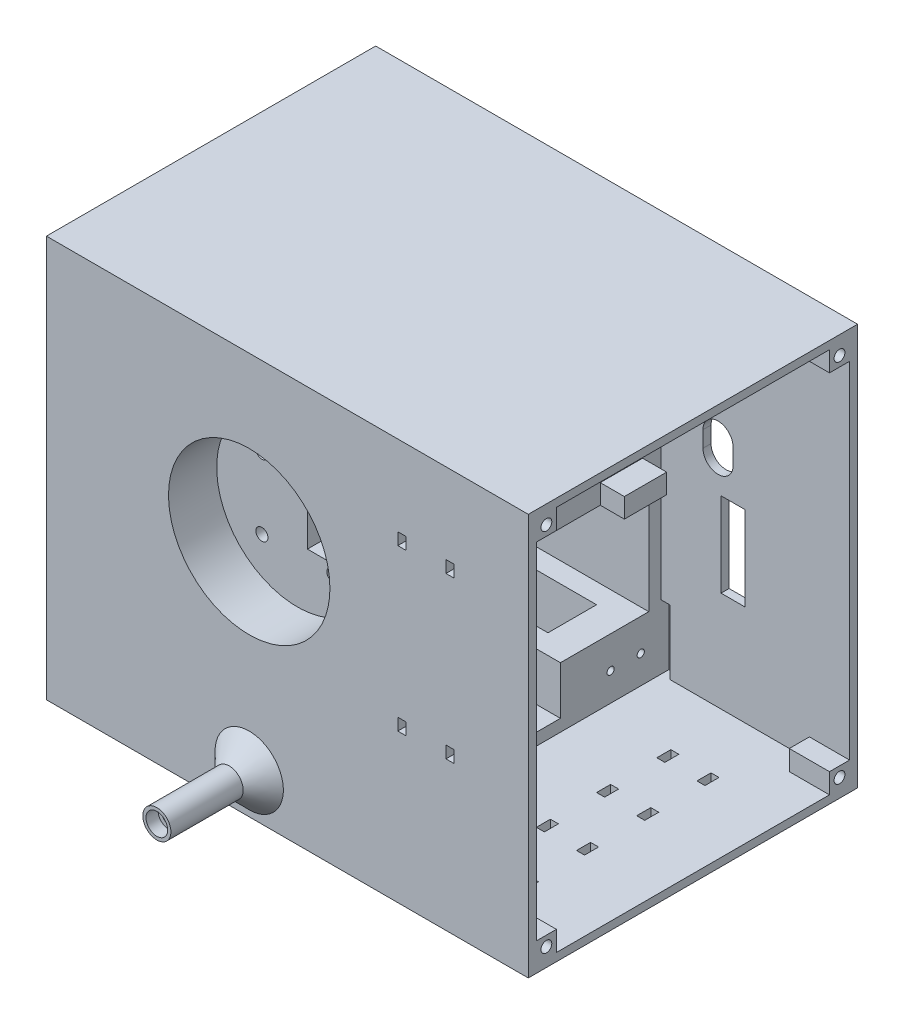
SolidWorks part; units mm, degrees
ref_plane "Plan de face" through (0, 0, 0) normal (0, 0, 1) x (1, 0, 0)
ref_plane "Plan de dessus" through (0, 0, 0) normal (0, 1, 0) x (1, 0, 0)
ref_plane "Plan de droite" through (0, 0, 0) normal (1, 0, 0) x (0, 0, -1)
sketch "Esquisse1" plane through (0, 0, 0) normal (0, 0, 1) x (1, 0, 0)
  line L0 (8.8388, 18.2) -> (8.8388, 0.5223) construction
  line L5 (-22.5, 50) -> (22.5, -50) construction
  line L6 (-22.5, -50) -> (22.5, 50) construction
  line L7 (-10.15, 45) -> (10.15, 45) construction
  line L8 (-10.15, 45) -> (-10.15, 24.7) construction
  line L9 (-10.15, 24.7) -> (10.15, 24.7) construction
  line L10 (10.15, 45) -> (10.15, 24.7) construction
  line L11 (-10.15, 45) -> (10.15, 24.7) construction
  line L12 (-10.15, 24.7) -> (10.15, 45) construction
  line L13 (8.8388, 0.5223) -> (-8.8388, 0.5223) construction
  line L15 (-22.5, 50) -> (22.5, 50)
  line L16 (-22.5, 50) -> (-22.5, -50)
  line L17 (-22.5, -50) -> (22.5, -50)
  line L18 (22.5, 50) -> (22.5, -50)
  circle A0 centre (0, 9.3612) radius 20.1
  circle A1 centre (0, 9.3612) radius 12.5 construction
  circle A2 centre (8.8388, 18.2) radius 1.5
  circle A3 centre (8.8388, 0.5223) radius 1.5
  circle A4 centre (-8.8388, 0.5223) radius 1.5
  circle A5 centre (-8.8388, 18.2) radius 1.5
  circle A6 centre (8.8388, 18.2) radius 3.5 construction
  point P7 (0, 34.85)
  point P32 (0, 0)
  dimension "D1" = 40.2
  dimension "D6" = 3
  dimension "D7" = 25
  dimension "D8" = 7
  dimension "D5" = 6.5
  dimension "D2" = 100
  dimension "D3" = 45
  dimension "D4" = 20.3
  dimension "D9" = 5
extrude "Boss.-Extru.1" add sketch "Esquisse1" along normal blind 12 contours L18 L15 L16 L17 A0 L7 L10 L9 L8 | L10 L7 L8 L9 region at (0, 48.9034, 0)
extrude "Boss.-Extru.4" add sketch "Esquisse1<3>" against normal blind 5 contours A0 | L18 L15 L16 L17 A0 L7 L10 L9 L8 region at (0, 48.9034, 0) region at (0, 9.3612, 0)
sketch "Esquisse1<3>" plane through (0, 0, 0) normal (0, 0, 1) x (1, 0, 0) same geometry as "Esquisse1"
sketch "Esquisse4" plane through (0, 0, -5) normal (0, 0, -1) x (-1, 0, 0)
  line L2 (-10, 45) -> (10, 25) construction
  line L4 (-22.5, 50) -> (-22.5, -50)
  line L5 (-22.5, -50) -> (22.5, -50)
  line L6 (22.5, -50) -> (22.5, 50)
  line L7 (22.5, 50) -> (-22.5, 50)
  line L8 (-22.5, 50) -> (-22.5, -50)
  line L9 (-22.5, -50) -> (22.5, -50)
  line L10 (22.5, -50) -> (22.5, 50)
  line L11 (22.5, 50) -> (-22.5, 50)
  line L15 (-10, 45) -> (10, 45)
  line L19 (-10, 45) -> (-10, 25)
  line L20 (-10, 25) -> (10, 25)
  line L21 (10, 45) -> (10, 25)
  circle A1 centre (8.8388, 18.2) radius 3.5
  circle A2 centre (8.8388, 0.5223) radius 3.5
  circle A3 centre (-8.8388, 0.5223) radius 3.5
  circle A4 centre (-8.8388, 18.2) radius 3.5
  point P17 (0, 35)
  line M10 (-22.5, 50) -> (-22.5, -50)
  line M11 (-22.5, -50) -> (22.5, -50)
  line M12 (22.5, -50) -> (22.5, 50)
  line M13 (22.5, 50) -> (-22.5, 50)
  dimension "D2" = 7
  dimension "D3" = 20
  dimension "D4" = 5
  dimension "D1" = 0
extrude "Boss.-Extru.5" add sketch "Esquisse4" along normal blind 65 contours A1 M13 M10 M11 M12 region at (0, -3.913, -5)
ref_plane "Plan1" through (-14.5, -50, -60) normal (0, 0, 1) x (1, 0, 0)
sketch "Esquisse6" plane through (0, -50, 0) normal (0, -1, 0) x (1, 0, 0)
  line L0 (0, -70) -> (0, 12) construction
  line L1 (22.5, -70) -> (-22.5, -70) construction
  line L2 (-22.5, 12) -> (22.5, 12) construction
  line L3 (-14.5, -47.9) -> (14.5, -47.9)
  line L4 (-14.5, -47.9) -> (-14.5, -60)
  line L5 (-14.5, -60) -> (14.5, -60)
  line L6 (14.5, -47.9) -> (14.5, -60)
  line L7 (-14.5, -47.9) -> (14.5, -60) construction
  line L8 (-14.5, -60) -> (14.5, -47.9) construction
  point P5 (0, -53.95)
  dimension "D1" = 12.1
  dimension "D2" = 29
  dimension "D3" = 10
extrude "Enlèv. mat.-Extru.1" cut sketch "Esquisse6" against normal blind 46
sketch "Esquisse7" plane through (-22.5, 0, 0) normal (-1, 0, 0) x (0, 0, 1)
  line L0 (12, 50) -> (-70, -50) construction
  line L1 (12, 50) -> (-70, 50)
  line L2 (12, 50) -> (12, -50)
  line L3 (12, -50) -> (-70, -50)
  line L4 (-70, 50) -> (-70, -50)
  line L5 (10, 48) -> (10, -48)
  line L10 (8.1701, 41.2587) -> (-66.1701, -41.2587) construction
  line L11 (8.1701, -41.2587) -> (-66.1701, 41.2587) construction
  line L12 (10, -48) -> (-68, -48)
  line L13 (-68, 48) -> (-68, -48)
  line L14 (10, 48) -> (-68, 48)
  point P6 (-29, 0)
  dimension "D1" = 2
extrude "Boss.-Extru.6" add sketch "Esquisse7" along normal blind 28
sketch "Esquisse8" plane through (22.5, 0, 0) normal (1, 0, 0) x (0, 0, -1)
  line L0 (-12, -50) -> (70, 50) construction
  line L1 (-10, -48) -> (-10, 48)
  line L2 (-12, -50) -> (70, -50)
  line L3 (-12, -50) -> (-12, 50)
  line L4 (-12, 50) -> (70, 50)
  line L5 (70, -50) -> (70, 50)
  line L6 (-10, 48) -> (68, 48)
  line L7 (68, -48) -> (68, 48)
  line L8 (-10, -48) -> (68, -48)
  dimension "D1" = 2
extrude "Boss.-Extru.7" add sketch "Esquisse8" along normal blind 47
sketch "Esquisse9" plane through (22.5, 0, 0) normal (1, 0, 0) x (0, 0, -1)
  line L0 (-10, 48) -> (-10, -48) construction
  line L1 (-4, 3) -> (6, 3)
  line L2 (-4, 3) -> (-4, 15.5)
  line L3 (-4, 15.5) -> (6, 15.5)
  line L4 (6, 3) -> (6, 15.5)
  line L5 (68, 48) -> (-10, 48) construction
  dimension "D1" = 12.5
  dimension "D2" = 10
  dimension "D3" = 6
  dimension "D4" = 32.5
extrude "Enlèv. mat.-Extru.2" cut sketch "Esquisse9" against normal blind 20
sketch "Esquisse10" plane through (0, 0, 10) normal (0, 0, -1) x (-1, 0, 0)
  line L0 (-44, 48) -> (-44, -48) construction
  line L1 (-69.5, 48) -> (-22.5, 48) construction
  line L2 (-69.5, -48) -> (-22.5, -48) construction
  line L3 (-22.5, -48) -> (-22.5, 48) construction
  line L4 (-69.5, -48) -> (-22.5, -48) construction
  line L5 (-49, -13) -> (-51, -13)
  line L6 (-49, -13) -> (-49, -10)
  line L7 (-49, -10) -> (-51, -10)
  line L8 (-51, -13) -> (-51, -10)
  line L9 (-49, 27) -> (-49, 30)
  line L10 (-49, 27) -> (-51, 27)
  line L11 (-51, 27) -> (-51, 30)
  line L12 (-49, 30) -> (-51, 30)
  line L13 (-49, -13) -> (-49, 27) construction
  line L14 (-37, -13) -> (-37, -10)
  line L15 (-39, -10) -> (-37, -10)
  line L16 (-39, -13) -> (-39, -10)
  line L17 (-39, -13) -> (-37, -13)
  line L18 (-39, -13) -> (-39, 27) construction
  line L19 (-39, 30) -> (-37, 30)
  line L20 (-37, 27) -> (-37, 30)
  line L21 (-39, 27) -> (-37, 27)
  line L22 (-39, 27) -> (-39, 30)
  dimension "D1" = 21.5
  dimension "D2" = 5
  dimension "D3" = 3
  dimension "D4" = 2
  dimension "D5" = 35
  dimension "D7" = 40
  dimension "D6" = 2
extrude "Enlèv. mat.-Extru.3" cut sketch "Esquisse10" against normal up to next
sketch "Esquisse11" plane through (22.5, 0, 0) normal (1, 0, 0) x (0, 0, -1)
  line L0 (-7, -45) -> (43, -45)
  line L5 (43, -45) -> (43, -33)
  line L6 (43, -33) -> (65, -33)
  line L7 (65, -33) -> (65, -4)
  line L8 (65, -4) -> (18, -4)
  line L9 (18, -4) -> (18, -20)
  line L10 (18, -20) -> (-7, -20)
  line L11 (-7, -20) -> (-7, -45)
  line L12 (-10, -48) -> (68, -48) construction
  line L13 (-10, 48) -> (-10, -48) construction
  line L14 (68, -48) -> (68, 48) construction
  dimension "D1" = 3
  dimension "D2" = 3
  dimension "D3" = 25
  dimension "D4" = 3
  dimension "D5" = 15
  dimension "D6" = 25
  dimension "D7" = 25
  dimension "D8" = 41
extrude "Enlèv. mat.-Extru.4" cut sketch "Esquisse11" against normal blind 40
sketch "Esquisse12" plane through (-17.5, 0, 0) normal (1, 0, 0) x (0, 0, -1)
  line L0 (62, -32) -> (-4, -32) construction
  line L1 (-7, -45) -> (43, -45)
  line L2 (-7, -45) -> (-7, -32)
  line L3 (-7, -32) -> (43, -32)
  line L4 (43, -45) -> (43, -32)
  line L5 (43, -45) -> (43, -33) construction
extrude "Enlèv. mat.-Extru.5" cut sketch "Esquisse12" against normal up to next
sketch "Esquisse13" plane through (0, -50, 0) normal (0, -1, 0) x (1, 0, 0)
  line L0 (46, -68) -> (46, 10) construction
  line L1 (69.5, -68) -> (22.5, -68) construction
  line L2 (69.5, 10) -> (22.5, 10) construction
  line L3 (50, -38) -> (50, -34.5)
  line L4 (50, -53) -> (52, -53)
  line L5 (50, -53) -> (50, -49.5)
  line L6 (50, -49.5) -> (52, -49.5)
  line L7 (52, -53) -> (52, -49.5)
  line L8 (50, -38) -> (52, -38)
  line L9 (52, -38) -> (52, -34.5)
  line L10 (50, -34.5) -> (52, -34.5)
  line L11 (50, -23) -> (50, -19.5)
  line L12 (50, -23) -> (52, -23)
  line L13 (52, -23) -> (52, -19.5)
  line L14 (50, -19.5) -> (52, -19.5)
  line L15 (50, -8) -> (50, -4.5)
  line L16 (50, -8) -> (52, -8)
  line L17 (52, -8) -> (52, -4.5)
  line L18 (50, -4.5) -> (52, -4.5)
  line L19 (50, -53) -> (50, -38) construction
  line L20 (42, -53) -> (42, -38) construction
  line L21 (42, -4.5) -> (40, -4.5)
  line L22 (40, -8) -> (40, -4.5)
  line L23 (42, -8) -> (40, -8)
  line L24 (42, -8) -> (42, -4.5)
  line L25 (42, -19.5) -> (40, -19.5)
  line L26 (40, -23) -> (40, -19.5)
  line L27 (42, -23) -> (40, -23)
  line L28 (42, -23) -> (42, -19.5)
  line L29 (42, -34.5) -> (40, -34.5)
  line L30 (40, -38) -> (40, -34.5)
  line L31 (42, -38) -> (40, -38)
  line L32 (40, -53) -> (40, -49.5)
  line L33 (42, -49.5) -> (40, -49.5)
  line L34 (42, -53) -> (42, -49.5)
  line L35 (42, -53) -> (40, -53)
  line L36 (42, -38) -> (42, -34.5)
  dimension "D1" = 4
  dimension "D2" = 2
  dimension "D3" = 3.5
  dimension "D4" = 15
  dimension "D6" = 15
  dimension "D5" = 4
extrude "Enlèv. mat.-Extru.6" cut sketch "Esquisse13" against normal up to next
sketch "Esquisse14" plane through (22.5, 0, 0) normal (1, 0, 0) x (0, 0, -1)
  line L5 (-10, -48) -> (68, -48) construction
  line L6 (68, -48) -> (68, 48) construction
  circle A0 centre (14, -12) radius 3.5
  circle A1 centre (14, -12) radius 1.375
  circle A3 centre (60, 38) radius 3.5
  circle A4 centre (60, 38) radius 1.375
  dimension "D1" = 2.75
  dimension "D2" = 7
  dimension "D3" = 36
  dimension "D4" = 54
  dimension "D5" = 46
  dimension "D6" = 50
extrude "Boss.-Extru.8" add sketch "Esquisse14" along normal blind 6
sketch "Esquisse15" plane through (22.5, 0, 0) normal (1, 0, 0) x (0, 0, -1)
  line L0 (65, -4) -> (18, -4) construction
  line L1 (63.4544, -4) -> (52.9202, -4)
  line L2 (63.4544, -4) -> (63.4544, 0.874)
  line L3 (63.4544, 0.874) -> (52.9202, 0.874)
  line L4 (52.9202, -4) -> (52.9202, 0.874)
  line L6 (11, 41) -> (19.6788, 41)
  line L7 (11, 41) -> (11, 30.8965)
  line L8 (11, 30.8965) -> (19.6788, 30.8965)
  line L9 (19.6788, 41) -> (19.6788, 30.8965)
extrude "Boss.-Extru.9" add sketch "Esquisse15" along normal blind 6
sketch "Esquisse17" plane through (0, 0, -68) normal (0, 0, 1) x (1, 0, 0)
  line L1 (37.5, -23) -> (43.5, -23)
  line L2 (37.5, -23) -> (37.5, -2)
  line L3 (37.5, -2) -> (43.5, -2)
  line L4 (43.5, -23) -> (43.5, -2)
  line L5 (22.5, -48) -> (22.5, 48) construction
  line L6 (69.5, -48) -> (22.5, -48) construction
  dimension "D1" = 6
  dimension "D2" = 21
  dimension "D3" = 15
  dimension "D4" = 25
extrude "Enlèv. mat.-Extru.7" cut sketch "Esquisse17" against normal up to next
sketch "Esquisse19" plane through (0, 0, 12) normal (0, 0, 1) x (1, 0, 0)
  line L1 (-50.5, -50) -> (69.5, -50) construction
  circle A0 centre (0, -40) radius 3.5
  circle A1 centre (0, -40) radius 1.7
  dimension "D1" = 7
  dimension "D3" = 3.4
  dimension "D2" = 10
extrude "Boss.-Extru.10" add sketch "Esquisse19" along normal blind 23
extrude "Enlèv. mat.-Extru.8" cut sketch "Esquisse19<2>" against normal up to next contours A1 region at (0, -40, 12)
sketch "Esquisse19<2>" plane through (0, 0, 12) normal (0, 0, 1) x (1, 0, 0) same geometry as "Esquisse19"
sketch "Esquisse20" plane through (0, 0, 35) normal (0, 0, 1) x (1, 0, 0)
  circle A0 centre (0, -40) radius 2.7
  dimension "D1" = 5.4
extrude "Enlèv. mat.-Extru.9" cut sketch "Esquisse20" against normal blind 3
sketch "Esquisse21" plane through (0, 0, 7) normal (0, 0, -1) x (-1, 0, 0)
  line L1 (-1.6166, -42.8) -> (1.6166, -42.8)
  line L2 (1.6166, -42.8) -> (3.2332, -40)
  line L3 (3.2332, -40) -> (1.6166, -37.2)
  line L4 (1.6166, -37.2) -> (-1.6166, -37.2)
  line L5 (-1.6166, -37.2) -> (-3.2332, -40)
  line L6 (-3.2332, -40) -> (-1.6166, -42.8)
  circle A0 centre (0, -40) radius 2.8 construction
  dimension "D1" = 5.6
extrude "Enlèv. mat.-Extru.10" cut sketch "Esquisse21" against normal blind 2.5
chamfer "Chanfrein1" distance 5 angle 45 1 edges at (3.5, -40, 12)
sketch "Esquisse23" plane through (0, 0, -70) normal (0, 0, -1) x (-1, 0, 0)
  line L0 (50.5, 50) -> (-69.5, 50) construction
  line L1 (-40.5, 13.75) -> (-33, 13.75)
  line L2 (-40.5, 13.75) -> (-40.5, 2.25)
  line L3 (-40.5, 2.25) -> (-33, 2.25)
  line L4 (-33, 13.75) -> (-33, 2.25)
  line L5 (-69.5, -50) -> (-69.5, 50) construction
  line L6 (-40.5, 8) -> (-33, 8) construction
  arc A0 (-40.5, 10) -> (-33, 10) centre (-36.75, 10) cw
  arc A1 (-40.5, 6) -> (-33, 6) centre (-36.75, 6) ccw
  dimension "D1" = 11.5
  dimension "D2" = 7.5
  dimension "D3" = 36.25
  dimension "D4" = 29
extrude "Enlèv. mat.-Extru.11" cut sketch "Esquisse23" against normal up to surface (2 mm away) contours L2 L6 L4 A0 | L6 L2 A1 L4 region at (36.75, 10.5435, -70) region at (36.75, 5.4565, -70) up to face at (40.5, -12.5, -68)
sketch "Esquisse24" plane through (-22.5, 0, 0) normal (-1, 0, 0) x (0, 0, 1)
  line L0 (7, -32) -> (-43, -32) construction
  line L1 (10, 48) -> (4.5, 48)
  line L2 (10, 48) -> (10, -32)
  line L3 (10, -32) -> (4.5, -32)
  line L4 (4.5, 48) -> (4.5, -32)
  line L6 (-68, 48) -> (-62.5, 48)
  line L7 (-68, 48) -> (-68, -32)
  line L8 (-68, -32) -> (-62.5, -32)
  line L9 (-62.5, 48) -> (-62.5, -32)
  dimension "D1" = 5.5
  dimension "D2" = 5.5
extrude "Boss.-Extru.11" add sketch "Esquisse24" along normal up to surface (28 mm away) up to face at (-50.5, 0, -29)
sketch "Esquisse25" plane through (0, 0, -68) normal (0, 0, 1) x (1, 0, 0)
  line L1 (-50.5, -48) -> (-45.5, -48)
  line L2 (-50.5, -48) -> (-50.5, -41)
  line L3 (-50.5, -41) -> (-45.5, -41)
  line L4 (-45.5, -48) -> (-45.5, -41)
  dimension "D1" = 7
  dimension "D2" = 5
extrude "Enlèv. mat.-Extru.12" cut sketch "Esquisse25" against normal up to surface (2 mm away) up to face at (36.75, 8, -70)
sketch "Esquisse26" plane through (0, 0, -70) normal (0, 0, -1) x (-1, 0, 0)
  line L1 (-22.5, -48) -> (-24.8, -48)
  line L2 (-22.5, -48) -> (-22.5, -31.9)
  line L3 (-22.5, -31.9) -> (-24.8, -31.9)
  line L4 (-24.8, -48) -> (-24.8, -31.9)
  dimension "D1" = 2.3
  dimension "D2" = 16.1
extrude "Enlèv. mat.-Extru.13" cut sketch "Esquisse26" against normal up to surface (2 mm away) up to face at (36.75, 8, -68)
sketch "Esquisse27" plane through (22.5, 0, 0) normal (1, 0, 0) x (0, 0, -1)
  line L0 (68, -41) -> (50.9775, -41) construction
  line L1 (68, -48) -> (68, 48) construction
  line L2 (-10, -48) -> (68, -48) construction
  circle A0 centre (63, -41) radius 0.9
  circle A1 centre (55.5, -41) radius 0.9
  dimension "D3" = 1.8
  dimension "D1" = 7
  dimension "D2" = 5
  dimension "D4" = 7.5
extrude "Enlèv. mat.-Extru.14" cut sketch "Esquisse27" against normal blind 8
sketch "Esquisse28" plane through (69.5, 0, 0) normal (1, 0, 0) x (0, 0, -1)
  line L0 (-10, -48) -> (-5, -43) construction
  line L1 (-10, -48) -> (-5, -48)
  line L2 (-10, -48) -> (-10, -43)
  line L3 (-10, -43) -> (-5, -43)
  line L4 (-5, -48) -> (-5, -43)
  line L5 (-10, 0) -> (70, 0) construction
  line L6 (-10, 48) -> (-10, -48) construction
  line L7 (70, -50) -> (70, 50) construction
  line L8 (29, -48) -> (29, 48) construction
  line L9 (-10, -48) -> (68, -48) construction
  line L10 (68, 48) -> (-10, 48) construction
  line L11 (-10, 43) -> (-5, 43)
  line L12 (-5, 48) -> (-5, 43)
  line L13 (-10, 48) -> (-5, 48)
  line L14 (-10, 48) -> (-10, 43)
  line L15 (86, -48) -> (81, -48)
  line L16 (86, -48) -> (86, -43)
  line L17 (86, -43) -> (81, -43)
  line L18 (81, -48) -> (81, -43)
  line L19 (-10, -43) -> (-5, -43)
  line L20 (-5, -48) -> (-5, -43)
  line L21 (-10, -48) -> (-5, -48)
  line L22 (-10, -48) -> (-10, -43)
  line L23 (68, -48) -> (63, -43) construction
  line L24 (68, -48) -> (68, -43)
  line L25 (68, -48) -> (63, -48)
  line L26 (63, -48) -> (63, -43)
  line L27 (68, -43) -> (63, -43)
  line L28 (68, 48) -> (68, 43)
  line L29 (68, 48) -> (63, 48)
  line L30 (63, 48) -> (63, 43)
  line L31 (68, 43) -> (63, 43)
  line L32 (63, -48) -> (63, -43)
  line L33 (68, -43) -> (63, -43)
  line L34 (68, -48) -> (68, -43)
  line L35 (68, -48) -> (63, -48)
  circle A0 centre (-7.5, -45.5) radius 1.35
  circle A1 centre (-7.5, 45.5) radius 1.35
  circle A2 centre (83.5, -45.5) radius 1.35
  circle A3 centre (65.5, 45.5) radius 1.35
  circle A4 centre (65.5, -45.5) radius 1.35
  line M12 (68, -48) -> (-10, -48)
  line M13 (-10, -48) -> (-10, 48)
  line M14 (-10, 48) -> (68, 48)
  line M15 (68, 48) -> (68, -48)
  dimension "D1" = 2.7
  dimension "D2" = 5
extrude "Boss.-Extru.12" add sketch "Esquisse28" against normal blind 10 contours L4 L3 A0 M12 M13 | L12 L11 A1 M14 M13 | L31 L30 A3 M15 M14 | L27 L26 A4 M15 M12 region at (69.5, -45.5, 9.9293) region at (69.5, -45.5, -63.0707) region at (69.5, 45.5, 9.9293) region at (69.5, 43.0707, -65.5)
sketch "Esquisse29" plane through (-50.5, 0, 0) normal (-1, 0, 0) x (0, 0, 1)
  line L0 (-65.5, 45.5) -> (-65.5, -29.5) construction
  circle A0 centre (7.5, 45.5) radius 1.35
  circle A1 centre (-65.5, 45.5) radius 1.35
  circle A2 centre (7.5, 45.5) radius 1.35 construction
  circle A3 centre (-65.5, -29.5) radius 1.35
  circle A4 centre (7.5, -29.5) radius 1.35
  dimension "D2" = 75
  dimension "D1" = 2
extrude "Enlèv. mat.-Extru.15" cut sketch "Esquisse29" against normal blind 10
sketch "Esquisse30" plane through (0, 0, -70) normal (0, 0, -1) x (-1, 0, 0)
  line L0 (10, 45) -> (-10, 25) construction
  line L1 (-59.5, 48) -> (-22.5, 48) construction
  line L2 (-27.5, 24.7) -> (27.5, 24.7) construction
  line L3 (-27.5, 24.7) -> (-27.5, 45.3) construction
  line L4 (-27.5, 45.3) -> (27.5, 45.3) construction
  line L5 (27.5, 24.7) -> (27.5, 45.3) construction
  line L6 (-27.5, 24.7) -> (27.5, 45.3) construction
  line L7 (-27.5, 45.3) -> (27.5, 24.7) construction
  line L8 (-30.6177, 45.3) -> (-29.0588, 42.6) construction
  line L9 (-29.0588, 42.6) -> (-25.9412, 42.6) construction
  line L10 (-25.9412, 42.6) -> (-24.3823, 45.3) construction
  line L11 (-24.3823, 45.3) -> (-25.9412, 48) construction
  line L12 (-25.9412, 48) -> (-29.0588, 48) construction
  line L13 (-29.0588, 48) -> (-30.6177, 45.3) construction
  circle A0 centre (27.5, 45.3) radius 1.7
  circle A1 centre (27.5, 24.7) radius 1.7
  circle A2 centre (-27.5, 24.7) radius 1.7
  circle A3 centre (-27.5, 45.3) radius 1.7
  circle A4 centre (-27.5, 45.3) radius 2.7 construction
  point P4 (0, 35)
  dimension "D1" = 3.4
  dimension "D2" = 5.4
  dimension "D3" = 55
extrude "Enlèv. mat.-Extru.16" cut sketch "Esquisse30" against normal up to next
sketch "Esquisse31" plane through (0, 0, -68) normal (0, 0, 1) x (1, 0, 0)
  line L0 (32.5, 48) -> (22.5, 41) construction
  line L1 (22.5, 48) -> (32.5, 48)
  line L2 (22.5, 48) -> (22.5, 41)
  line L3 (22.5, 41) -> (32.5, 41)
  line L4 (32.5, 48) -> (32.5, 41)
  line L5 (27.5, 45.3) -> (27.5, 24.7) construction
  line L6 (27.5, 35) -> (22.5, 35) construction
  line L7 (22.5, 48) -> (22.5, -48) construction
  line L8 (59.5, 48) -> (22.5, 48) construction
  line L9 (25.9412, 48) -> (24.3823, 45.3)
  line L10 (24.3823, 45.3) -> (25.9412, 42.6)
  line L11 (25.9412, 42.6) -> (29.0588, 42.6)
  line L12 (29.0588, 42.6) -> (30.6177, 45.3)
  line L13 (30.6177, 45.3) -> (29.0588, 48)
  line L14 (29.0588, 48) -> (25.9412, 48)
  line L15 (32.5, 22) -> (22.5, 29) construction
  line L16 (29.0588, 22) -> (25.9412, 22)
  line L17 (30.6177, 24.7) -> (29.0588, 22)
  line L18 (29.0588, 27.4) -> (30.6177, 24.7)
  line L19 (25.9412, 27.4) -> (29.0588, 27.4)
  line L20 (24.3823, 24.7) -> (25.9412, 27.4)
  line L21 (25.9412, 22) -> (24.3823, 24.7)
  line L22 (32.5, 22) -> (32.5, 29)
  line L23 (22.5, 29) -> (32.5, 29)
  line L24 (22.5, 22) -> (22.5, 29)
  line L25 (22.5, 22) -> (32.5, 22)
  line L27 (32.5, 22) -> (22.5, 22)
  line L28 (32.5, 22) -> (32.5, 20.4)
  line L29 (32.5, 20.4) -> (22.5, 20.4)
  line L30 (22.5, 22) -> (22.5, 20.4)
  circle A0 centre (27.5, 45.3) radius 2.7 construction
  circle A1 centre (27.5, 24.7) radius 2.7 construction
  point P5 (27.5, 44.5)
  point P6 (27.5, 45.3)
  point P37 (27.5, 24.7)
  point P38 (27.5, 25.5)
  line M16 (59.5, 48) -> (22.5, 48)
  line M17 (22.5, 48) -> (22.5, -31.9)
  dimension "D1" = 7
  dimension "D2" = 10
  dimension "D3" = 1.6
extrude "Boss.-Extru.13" add sketch "Esquisse31" along normal blind 3 contours L25 L21 L20 L19 L18 L17 L22 L23 M17 | L29 L28 L25 L16 M17 | L13 L12 L11 L10 L9 L1 L3 L4 M17 M16 region at (27.5, 28.8779, -68) region at (24.2206, 47.8779, -68) region at (27.5, 21.2, -68)
sketch "Esquisse32" plane through (0, 0, -62.5) normal (0, 0, 1) x (1, 0, 0)
  line L0 (-50.5, 48) -> (-22.5, 48) construction
  line L1 (-29.0588, 48) -> (-30.6177, 45.3)
  line L2 (-30.6177, 45.3) -> (-29.0588, 42.6)
  line L3 (-29.0588, 42.6) -> (-25.9412, 42.6)
  line L4 (-25.9412, 42.6) -> (-24.3823, 45.3)
  line L5 (-24.3823, 45.3) -> (-25.9412, 48)
  line L6 (-25.9412, 48) -> (-29.0588, 48)
  line L7 (-27.5, 45.3) -> (-27.5, 24.7) construction
  line L8 (-27.5, 35) -> (-22.5, 35) construction
  line L9 (-22.5, 48) -> (-22.5, -32) construction
  line L10 (-25.9412, 22) -> (-29.0588, 22)
  line L11 (-24.3823, 24.7) -> (-25.9412, 22)
  line L12 (-25.9412, 27.4) -> (-24.3823, 24.7)
  line L13 (-29.0588, 27.4) -> (-25.9412, 27.4)
  line L14 (-30.6177, 24.7) -> (-29.0588, 27.4)
  line L15 (-29.0588, 22) -> (-30.6177, 24.7)
  circle A0 centre (-27.5, 45.3) radius 2.7 construction
  circle A1 centre (-27.5, 24.7) radius 2.7 construction
extrude "Enlèv. mat.-Extru.17" cut sketch "Esquisse32" against normal blind 4
